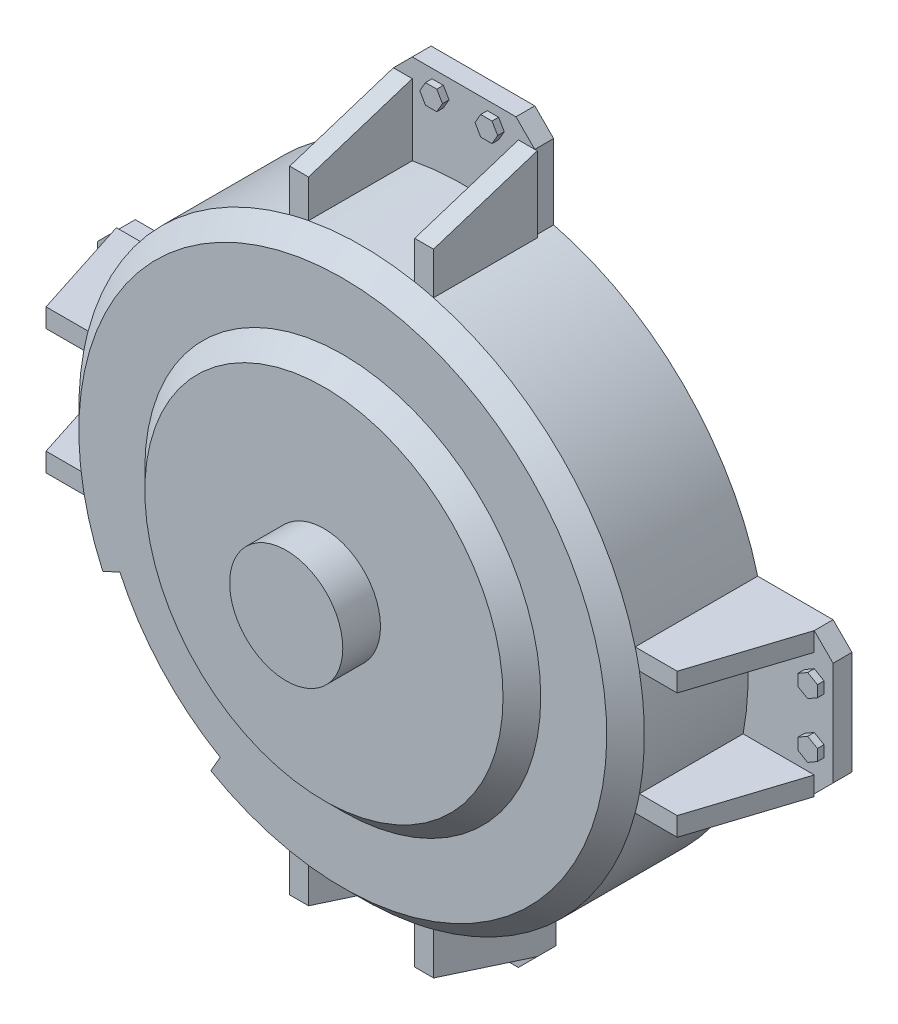
SolidWorks part; units mm, degrees
ref_plane "Plan de face" through (0, 0, 0) normal (0, 0, 1) x (1, 0, 0)
ref_plane "Plan de dessus" through (0, 0, 0) normal (0, 1, 0) x (1, 0, 0)
ref_plane "Plan de droite" through (0, 0, 0) normal (1, 0, 0) x (0, 0, -1)
sketch "Esquisse1" plane through (0, 0, 0) normal (0, 0, 1) x (1, 0, 0)
  circle A0 centre (0, 0) radius 150
  dimension "D1" = 300
extrude "Boss.-Extru.1" add sketch "Esquisse1" along normal blind 75
chamfer "Chanfrein1" distance 10 angle 45 1 edges at (150, 0, 75)
sketch "Esquisse2" plane through (0, 0, 0) normal (0, 0, -1) x (-1, 0, 0)
  line L0 (0, 0) -> (-150, 0) construction
  line L2 (-195.0678, 38.1489) -> (-145.0678, 38.1489)
  line L3 (-195.0678, 38.1489) -> (-195.0678, -36.8511)
  line L4 (-195.0678, -36.8511) -> (-145.4029, -36.8511)
  line L5 (-115, -7.2869) -> (-115, -12.0019)
  circle A0 centre (0, 0) radius 150 construction
  arc A1 (-145.0678, 38.1489) -> (-145.4029, -36.8511) centre (0, 0) ccw
  dimension "D1" = 75
  dimension "D2" = 50
extrude "Boss.-Extru.2" add sketch "Esquisse2" against normal blind 10 contours A1 L4 L3 L2
chamfer "Chanfrein2" distance 10 angle 45 2 edges at (195.0678, -36.8511, 5) (195.0678, 38.1489, 5)
sketch "Esquisse3" plane through (0, 38.1489, 0) normal (0, 1, 0) x (1, 0, 0)
  line L0 (185.0678, -10) -> (145.0678, -10)
  line L1 (145.0678, -10) -> (145.0678, -65)
  line L2 (150, -65) -> (-150, -65) construction
  line L3 (145.0678, -65) -> (167.3878, -65)
  line L4 (167.3878, -65) -> (185.0678, -10)
  line L5 (185.0678, -10) -> (185.0678, 0) construction
  line L6 (185.0678, -10) -> (145.0678, -10) construction
  dimension "D1" = 17.68
extrude "Boss.-Extru.3" add sketch "Esquisse3" against normal blind 10
sketch "Esquisse4" plane through (0, 0, 10) normal (0, 0, 1) x (1, 0, 0)
  line L0 (185.0678, -36.8511) -> (185.0678, 98.5871) construction
  line L1 (185.0678, 28.1489) -> (147.3351, 28.1489) construction
  line L8 (185.0678, 20.6489) -> (179.8716, 17.6489)
  line L9 (179.8716, 17.6489) -> (179.8716, 11.6489)
  line L10 (179.8716, 11.6489) -> (185.0678, 8.6489)
  line L11 (185.0678, 8.6489) -> (190.2639, 11.6489)
  line L12 (190.2639, 11.6489) -> (190.2639, 17.6489)
  line L13 (190.2639, 17.6489) -> (185.0678, 20.6489)
  circle A0 centre (185.0678, 14.6489) radius 5.1962 construction
  dimension "D1" = 6
  dimension "D2" = 7.5
extrude "Boss.-Extru.4" add sketch "Esquisse4" along normal blind 3.5
mirror "Symétrie1" about plane through (0, 0, 0) normal (0, 1, 0) of "Boss.-Extru.4", "Boss.-Extru.3"
pattern_circular "Répétition circulaire1" count 4 every 90 about axis through (0, 0, 0) along (0, 0, 1) of "Boss.-Extru.2", "Chanfrein2", "Boss.-Extru.3", "Boss.-Extru.4", "Symétrie1"
sketch "Esquisse5" plane through (0, 0, 75) normal (0, 0, 1) x (1, 0, 0)
  line L0 (0, 0) -> (-226.3146, 0) construction
  line L1 (0, 0) -> (0, -302.4544) construction
  line L2 (-118.1912, -54.1371) -> (-136.3745, -62.4659)
  line L3 (-65, -112.5833) -> (-75, -129.9038)
  arc A0 (-118.1912, -54.1371) -> (-65, -112.5833) centre (0, 0) ccw
  arc A1 (-145.0678, -38.1489) -> (-38.1489, -145.0678) centre (0, 0) ccw construction
  arc A2 (-136.3745, -62.4659) -> (-75, -129.9038) centre (0, 0) ccw
  dimension "D3" = 260
  dimension "D1" = 30
  dimension "D2" = 24.61
extrude "Enlèv. mat.-Extru.1" cut sketch "Esquisse5" against normal blind 60
sketch "Esquisse6" plane through (0, 0, 75) normal (0, 0, 1) x (1, 0, 0)
  circle A0 centre (0, 0) radius 110
  dimension "D1" = 220
extrude "Boss.-Extru.5" add sketch "Esquisse6" along normal blind 10
chamfer "Chanfrein3" distance 15 angle 45 1 edges at (110, 0, 85)
sketch "Esquisse7" plane through (0, 0, 85) normal (0, 0, 1) x (1, 0, 0)
  circle A0 centre (0, 0) radius 30
  dimension "D1" = 60
extrude "Boss.-Extru.6" add sketch "Esquisse7" along normal blind 20
